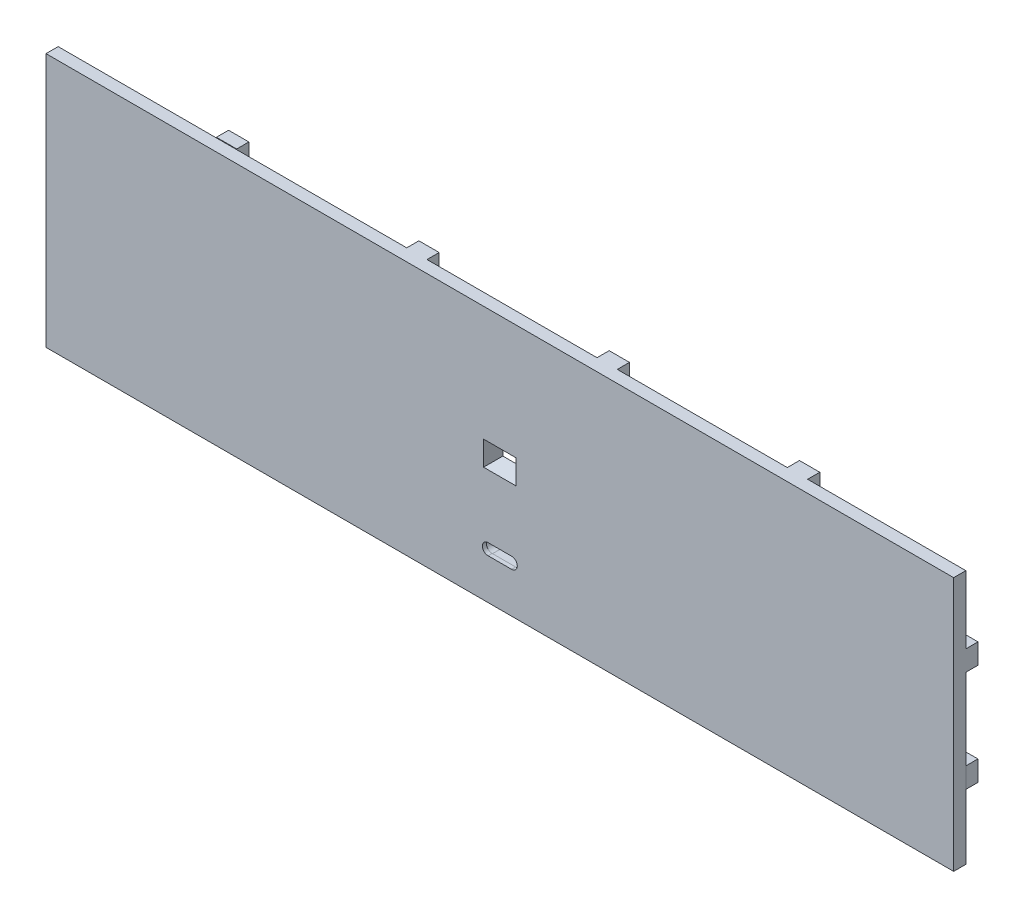
SolidWorks part; units mm, degrees
ref_plane "前视基准面" through (0, 0, 0) normal (0, 0, 1) x (1, 0, 0)
ref_plane "上视基准面" through (0, 0, 0) normal (0, 1, 0) x (1, 0, 0)
ref_plane "右视基准面" through (0, 0, 0) normal (1, 0, 0) x (0, 0, -1)
sketch "草图1" plane through (0, 0, 0) normal (0, 0, 1) x (1, 0, 0)
  line L1 (-111.85, 31.35) -> (111.85, 31.35)
  line L2 (-111.85, 31.35) -> (-111.85, -31.35)
  line L3 (-111.85, -31.35) -> (111.85, -31.35)
  line L4 (111.85, 31.35) -> (111.85, -31.35)
  line L5 (-111.85, 31.35) -> (111.85, -31.35) construction
  line L6 (-111.85, -31.35) -> (111.85, 31.35) construction
  point P0 (0, 0)
  dimension "D1" = 223.7
  dimension "D2" = 62.7
extrude "凸台-拉伸1" add sketch "草图1" against normal blind 3
sketch "草图2" plane through (0, 0, 0) normal (0, 0, 1) x (1, 0, 0)
  line L0 (-2.9, -19.95) -> (2.9, -19.95) construction
  line L1 (-2.9, -18.55) -> (2.9, -18.55)
  line L2 (-2.9, -21.35) -> (2.9, -21.35)
  line L3 (-111.85, -31.35) -> (111.85, -31.35) construction
  arc A0 (-2.9, -18.55) -> (-2.9, -21.35) centre (-2.9, -19.95) ccw
  arc A1 (2.9, -21.35) -> (2.9, -18.55) centre (2.9, -19.95) ccw
  point P2 (0, -19.95)
  dimension "D1" = 1.4
  dimension "D2" = 5.8
  dimension "D3" = 10
extrude "切除-拉伸1" cut sketch "草图2" against normal blind 1
sketch "草图5" plane through (0, 0, -3) normal (0, 0, -1) x (-1, 0, 0)
  line L0 (3, -19.95) -> (-3, -19.95) construction
  line L1 (3, -21.55) -> (-3, -21.55)
  line L2 (3, -18.35) -> (-3, -18.35)
  line L5 (111.85, -31.35) -> (-111.85, -31.35) construction
  arc A1 (3, -21.55) -> (3, -18.35) centre (3, -19.95) ccw
  arc A2 (-3, -18.35) -> (-3, -21.55) centre (-3, -19.95) ccw
  point P5 (0, -19.95)
  dimension "D2" = 1.6
  dimension "D1" = 6
  dimension "D3" = 9.8
extrude "切除-拉伸3" cut sketch "草图5" against normal blind 2
extrude "拉伸-薄壁1" add sketch "草图5<2>" along normal blind 4 thin thin type one direction wall 3
sketch "草图5<2>" plane through (0, 0, -3) normal (0, 0, -1) x (-1, 0, 0) same geometry as "草图5"
sketch "草图11" plane through (0, 0, 0) normal (0, 0, 1) x (1, 0, 0)
  line L1 (-4, -3) -> (4, -3)
  line L2 (-4, -3) -> (-4, 3)
  line L3 (-4, 3) -> (4, 3)
  line L4 (4, -3) -> (4, 3)
  line L5 (-4, -3) -> (4, 3) construction
  line L6 (-4, 3) -> (4, -3) construction
  point P0 (0, 0)
  point P6 (0, 0)
  dimension "D1" = 8
  dimension "D2" = 6
sketch "草图12" plane through (0, 0, -3) normal (0, 0, -1) x (-1, 0, 0)
  line L0 (4, -3) -> (-4, 3) construction
  line L1 (-2.25, 1.25) -> (2.25, 1.25)
  line L2 (-2.25, 1.25) -> (-2.25, -1.25)
  line L3 (-2.25, -1.25) -> (2.25, -1.25)
  line L4 (2.25, 1.25) -> (2.25, -1.25)
  line L5 (-2.25, 1.25) -> (2.25, -1.25) construction
  line L6 (-2.25, -1.25) -> (2.25, 1.25) construction
  point P0 (0, 0)
  point P1 (0, 0)
  dimension "D1" = 4.5
  dimension "D2" = 2.5
loft "切除-放样1" cut profiles "草图11", "草图12" connector at (4, 3, 0) connector at (2.25, 1.25, -3)
sketch "草图13" plane through (0, 0, -3) normal (0, 0, -1) x (-1, 0, 0)
  line L0 (-111.85, -31.35) -> (-111.85, 31.35) construction
  line L1 (72.85, -31.35) -> (97.85, -31.35)
  line L2 (72.85, -31.35) -> (72.85, -21.35)
  line L3 (72.85, -21.35) -> (97.85, -21.35)
  line L4 (97.85, -31.35) -> (97.85, -21.35)
  line L6 (111.85, 31.35) -> (111.85, -31.35) construction
  line L7 (-97.85, -31.35) -> (-72.85, -31.35)
  line L8 (111.85, -31.35) -> (-111.85, -31.35) construction
  line L12 (-97.85, -31.35) -> (-97.85, -21.35)
  line L13 (-97.85, -21.35) -> (-72.85, -21.35)
  line L14 (-72.85, -31.35) -> (-72.85, -21.35)
  dimension "D1" = 10
  dimension "D2" = 25
  dimension "D3" = 14
  dimension "D4" = 10
  dimension "D5" = 25
  dimension "D6" = 14
extrude "凸台-拉伸2" add sketch "草图13" along normal blind 12
sketch "草图14" plane through (0, 0, -3) normal (0, 0, -1) x (-1, 0, 0)
  line L0 (-111.85, -31.35) -> (-111.85, 31.35) construction
  line L1 (-111.85, 9.65) -> (111.85, 9.65)
  line L2 (-111.85, 9.65) -> (-111.85, 14.65)
  line L3 (-111.85, 14.65) -> (111.85, 14.65)
  line L4 (111.85, 9.65) -> (111.85, 14.65)
  line L5 (111.85, 31.35) -> (111.85, -31.35) construction
  line L6 (-111.8284, 14.65) -> (111.8716, 14.65)
  line L7 (-111.8284, 9.65) -> (111.8716, 9.65)
  line L8 (-111.7853, 14.65) -> (111.8931, 14.65)
  line L9 (-111.8069, 9.65) -> (111.8931, 9.65)
  line L10 (-111.7853, 14.65) -> (111.9147, 14.65)
  line L11 (-111.7853, 9.65) -> (111.9147, 9.65)
  line L12 (-111.8284, -10.35) -> (111.8716, -10.35)
  line L13 (-111.8284, -15.35) -> (111.8716, -15.35)
  line L14 (-111.8069, -10.35) -> (111.8931, -10.35)
  line L15 (-111.8069, -15.35) -> (111.8931, -15.35)
  line L16 (-111.7853, -10.35) -> (111.9147, -10.35)
  line L17 (-111.7853, -15.35) -> (111.9147, -15.35)
  line L18 (-111.85, -10.35) -> (111.85, -10.35)
  line L19 (-111.85, -15.35) -> (111.85, -15.35)
  line L20 (-111.85, -15.35) -> (-111.8284, -10.35)
  line L21 (111.8931, -15.35) -> (111.9147, -10.35)
  line L23 (-72.85, -31.5) -> (-67.85, -31.5)
  line L24 (-72.85, -31.5) -> (-72.85, 31.5)
  line L25 (-72.85, 31.5) -> (-67.85, 31.5)
  line L26 (-67.85, -31.5) -> (-67.85, 31.5)
  line L28 (-25.95, -31.5) -> (-25.95, 31.5)
  line L29 (-20.95, -31.5) -> (-20.95, 31.5)
  line L30 (-25.95, -31.5) -> (-20.95, -31.5)
  line L31 (-25.95, 31.5) -> (-20.95, 31.5)
  line L32 (20.95, -31.5) -> (20.95, 31.5)
  line L33 (25.95, -31.5) -> (25.95, 31.5)
  line L34 (20.95, -31.5) -> (25.95, -31.5)
  line L35 (20.95, 31.5) -> (25.95, 31.5)
  line L36 (67.85, -31.5) -> (67.85, 31.5)
  line L37 (72.85, -31.5) -> (72.85, 31.5)
  line L38 (67.85, -31.5) -> (72.85, -31.5)
  line L39 (67.85, 31.5) -> (72.85, 31.5)
  line L40 (72.85, -21.35) -> (72.85, -31.35) construction
  line L41 (-72.85, -31.35) -> (-72.85, -21.35) construction
  line L42 (3, -15.35) -> (-3, -15.35) construction
  point P41 (0, -15.35)
  line M31 (-72.85, -31.35) -> (72.85, -31.35)
  line M34 (111.85, -31.35) -> (111.85, 31.35)
  line M35 (111.85, 31.35) -> (-111.85, 31.35)
  line M36 (-111.85, 31.35) -> (-111.85, -31.35)
  dimension "D1" = 5
  dimension "D4" = 5
  dimension "D2" = 4
  dimension "D3" = 2
  dimension "D6" = 4
extrude "凸台-拉伸3" add sketch "草图14" along normal blind 3 contours L37 L15 L14 M34 | L19 L37 L18 L36 | L37 L19 L36 M31 | L15 L36 L14 L33 | L9 L36 L6 L33 | L37 L9 L6 M34 | L9 L32 L6 L29 | L11 L33 L10 L32 | L10 L33 L32 M35 | L18 L33 L11 L32 | L19 L33 L18 L32 | L33 L19 L32 M31 | L15 L32 L14 L29 | L29 L19 L28 M31 | L19 L29 L18 L28 | L18 L29 L11 L28 | L11 L29 L10 L28 | L10 L29 L28 M35 | L9 L28 L6 L26 | L15 L28 L14 L26 | L26 L19 L24 M31 | L19 L26 L18 L24 | L18 L26 L11 L24 | L11 L26 L10 L24 | L10 L26 L24 M35 | L9 L24 L6 L3 L1 L7 M36 | L15 L24 L14 L12 L20 L19 L13 | L36 L39 L37 L38 region at (92.35, 12.15, -3) region at (92.3446, -12.8502, -3) region at (70.35, 23, -3) region at (70.35, 12.15, -3) region at (70.35, -0.35, -3) region at (46.9, 12.15, -3) region at (70.35, -12.85, -3) region at (23.45, 23, -3) region at (23.45, 12.15, -3) region at (23.45, -0.35, -3) region at (46.9, -12.85, -3) region at (70.35, -23.35, -3) region at (0, 12.15, -3) region at (23.45, -12.85, -3) region at (-23.45, 23, -3) region at (-23.45, 12.15, -3) region at (-23.45, -0.35, -3) region at (0, -12.85, -3) region at (23.45, -23.35, -3) region at (-46.9, 12.15, -3) region at (-23.45, -12.85, -3) region at (-46.9, -12.85, -3) region at (-23.45, -23.35, -3) region at (-92.35, 12.15, -3) region at (-70.35, -12.85, -3) region at (-92.35, -12.85, -3) region at (-70.35, -23.35, -3)
sketch "草图15" plane through (0, -31.35, 0) normal (0, -1, 0) x (-1, 0, 0)
  line L0 (111.85, 0) -> (-111.85, 0) construction
  line L5 (97.85, 15) -> (97.85, 3) construction
  line L8 (-97.85, 15) -> (-97.85, 3) construction
  circle A0 centre (85.35, 8) radius 2
  circle A1 centre (-85.35, 8) radius 2
  dimension "D1" = 4
  dimension "D4" = 4
  dimension "D2" = 8
  dimension "D3" = 12.5
  dimension "D5" = 8
  dimension "D6" = 12.5
extrude "切除-拉伸4" cut sketch "草图15" against normal blind 10
sketch "草图16" plane through (0, -31.35, 0) normal (0, -1, 0) x (1, 0, 0)
  line L1 (-83.3293, -11.5) -> (-81.3085, -8)
  line L2 (-81.3085, -8) -> (-83.3293, -4.5)
  line L3 (-83.3293, -4.5) -> (-87.3707, -4.5)
  line L4 (-87.3707, -4.5) -> (-89.3915, -8)
  line L5 (-89.3915, -8) -> (-87.3707, -11.5)
  line L6 (-87.3707, -11.5) -> (-83.3293, -11.5)
  line L7 (87.3707, -11.5) -> (89.3915, -8)
  line L8 (89.3915, -8) -> (87.3707, -4.5)
  line L9 (87.3707, -4.5) -> (83.3293, -4.5)
  line L10 (83.3293, -4.5) -> (81.3085, -8)
  line L11 (81.3085, -8) -> (83.3293, -11.5)
  line L12 (83.3293, -11.5) -> (87.3707, -11.5)
  circle A0 centre (-85.35, -8) radius 3.5 construction
  circle A1 centre (85.35, -8) radius 3.5 construction
  dimension "D1" = 3.5
  dimension "D2" = 3.5
extrude "切除-拉伸5" cut sketch "草图16" against normal blind 6
